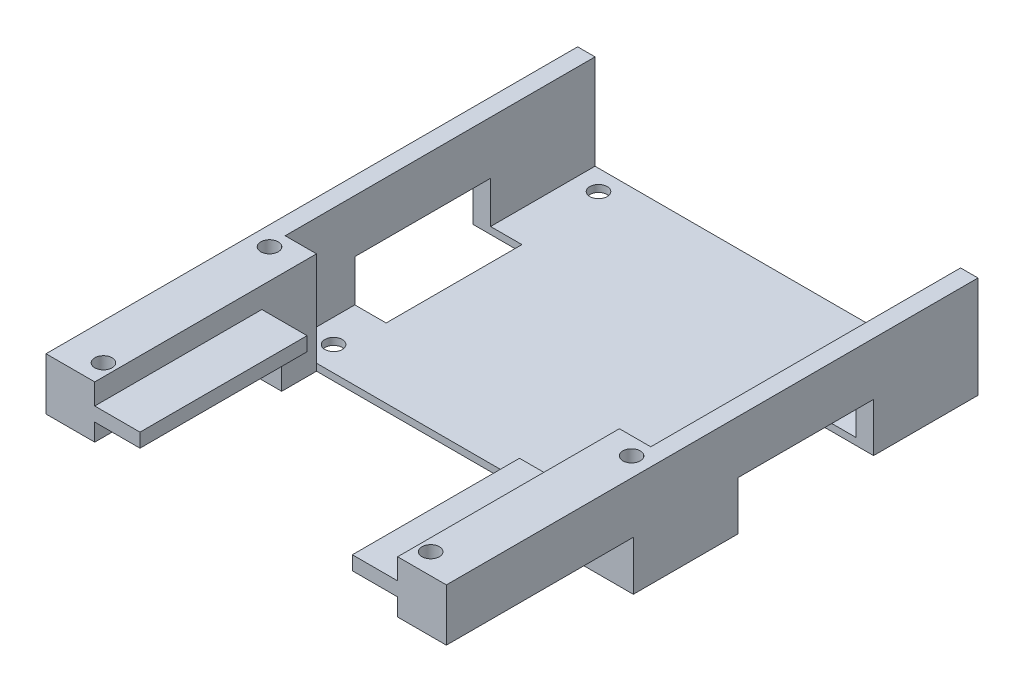
SolidWorks part; units mm, degrees
ref_plane "Front Plane" through (0, 0, 0) normal (0, 0, 1) x (1, 0, 0)
ref_plane "Top Plane" through (0, 0, 0) normal (0, 1, 0) x (1, 0, 0)
ref_plane "Right Plane" through (0, 0, 0) normal (1, 0, 0) x (0, 0, -1)
sketch "Sketch1" plane through (0, 0, 0) normal (0, 1, 0) x (1, 0, 0)
  line L0 (0, 0) -> (0, 76.35) construction
  line L1 (-28.75, 76.35) -> (28.75, 76.35)
  line L2 (28.75, 76.35) -> (28.75, 0)
  line L3 (28.75, 0) -> (21.75, 0)
  line L4 (21.75, 0) -> (21.75, 31.85)
  line L5 (21.75, 31.85) -> (-21.75, 31.85)
  line L6 (-21.75, 31.85) -> (-21.75, 0)
  line L7 (-21.75, 0) -> (-28.75, 0)
  line L8 (-28.75, 0) -> (-28.75, 76.35)
  line L9 (-26.25, 76.35) -> (-26.25, 31.85)
  line L14 (-26.25, 31.85) -> (-21.75, 31.85)
  line L15 (26.25, 76.35) -> (26.25, 31.85)
  line L16 (26.25, 31.85) -> (21.75, 31.85)
  line L17 (28.75, 74.35) -> (30.25, 74.35)
  line L18 (-28.75, 41.35) -> (-26.25, 41.35)
  line L19 (-28.75, 41.35) -> (-28.75, 53.35)
  line L20 (-28.75, 53.35) -> (-26.25, 53.35)
  line L21 (-26.25, 41.35) -> (-26.25, 53.35)
  line L22 (30.25, 68.35) -> (28.75, 68.35)
  line L23 (-30.25, 68.35) -> (-28.75, 68.35)
  line L24 (-28.75, 74.35) -> (-30.25, 74.35)
  arc A0 (30.25, 68.35) -> (30.25, 74.35) centre (30.25, 71.35) ccw
  arc A1 (-30.25, 68.35) -> (-30.25, 74.35) centre (-30.25, 71.35) cw
  point P10 (0, 76.35)
  point P16 (-27.5, 41.35)
  point P17 (-22.85, 73.45)
  point P18 (22.85, 73.45)
  point P23 (22.85, 35.4)
  point P24 (-22.85, 35.4)
  point P25 (23.5, 3)
  point P26 (26, 29.35)
  point P27 (-26, 29.35)
  point P28 (-23.5, 3)
  point P40 (30.25, 71.35)
  point P41 (-30.25, 71.35)
  dimension "D16" = 3
  dimension "D1" = 2.5
  dimension "D2" = 7
  dimension "D3" = 43.5
  dimension "D4" = 31.85
  dimension "D5" = 44.5
  dimension "D6" = 23
  dimension "D7" = 12
  dimension "D8" = 22.85
  dimension "D9" = 38.05
  dimension "D10" = 2.9
  dimension "D11" = 47
  dimension "D12" = 52
  dimension "D13" = 47
  dimension "D14" = 3
  dimension "D15" = 1.5
  dimension "D17" = 2
extrude "Boss-Extrude1" add sketch "Sketch1" along normal blind 1 contours L5 L0 L1 L9 L14 | L0 L5 L16 L15 L1 region at (-13.125, 0, -54.1) region at (13.125, 0, -54.1)
extrude "Boss-Extrude2" add sketch "Sketch1<3>" along normal blind 14.6 contours L18 L8 L7 L6 L14 L9 | L8 L20 L9 L1 | L15 L16 L4 L3 L2 L1 | L20 L8 L18 L9 region at (-27.5, 0, -64.85) region at (25.999, 0, -28.6329) region at (-27.5, 0, -47.35) region at (-25.4666, 0, -17.9154)
sketch "Sketch1<3>" plane through (0, 0, 0) normal (0, 1, 0) x (1, 0, 0) same geometry as "Sketch1"
hole_wizard "Ø2.5 (2.5) Diameter Hole1" positions "Sketch4" profile "Sketch5" hole size "Ø2.5" standard "ANSI Metric" end condition through all
sketch "Sketch4" plane through (0, 0, 0) normal (0, -1, 0) x (-1, 0, 0)
  point P0 (-22.85, 73.45)
  point P3 (22.85, 73.45)
  point P6 (26, 29.35)
  point P9 (22.85, 35.4)
  point P12 (-22.85, 35.4)
  point P15 (-26, 29.35)
  point P18 (-23.5, 3)
  point P21 (23.5, 3)
  point P24 (-30.25, 71.35)
  point P27 (30.25, 71.35)
sketch "Sketch5" plane through (22.85, 0, -73.45) normal (1, 0, 0) x (0, 0, -1)
  line L0 (0, 0) -> (0, 14.6)
  line L1 (0, 14.6) -> (1.25, 14.6)
  line L2 (1.25, 14.6) -> (1.25, 0)
  line L5 (1.25, 0) -> (0, 0)
  line L11 (0, -6.35) -> (0, 107.95) construction
  dimension "Thru Hole Dia." = 2.5
  dimension "Thru Hole Depth" = 14.6
sketch "Sketch6" plane through (0, 0, 0) normal (0, 0, 1) x (1, 0, 0)
  line L0 (-21.75, 14.6) -> (-21.75, 0) construction
  line L5 (0, -1.6497) -> (0, 21.9352) construction
  line L6 (-21.75, 9.6) -> (-15.25, 9.6)
  line L7 (-21.75, 9.6) -> (-21.75, 11.6)
  line L8 (-21.75, 11.6) -> (-15.25, 11.6)
  line L9 (-15.25, 9.6) -> (-15.25, 11.6)
  line L10 (-28.75, 14.6) -> (-28.75, 0) construction
  line L11 (-20.25, 9.6) -> (-21.75, 9.6)
  line L12 (-20.25, 9.6) -> (-20.25, 7.1)
  line L13 (-20.25, 7.1) -> (-21.75, 7.1)
  line L14 (-21.75, 9.6) -> (-21.75, 7.1)
  line L15 (-21.75, 0) -> (-28.75, 0)
  line L16 (-21.75, 0) -> (-21.75, 7.1)
  line L17 (-21.75, 7.1) -> (-28.75, 7.1)
  line L18 (-28.75, 0) -> (-28.75, 7.1)
  line L19 (28.75, 0) -> (28.75, 7.1)
  line L20 (21.75, 7.1) -> (28.75, 7.1)
  line L21 (21.75, 0) -> (21.75, 7.1)
  line L22 (21.75, 0) -> (28.75, 0)
  line L23 (21.75, 9.6) -> (21.75, 7.1)
  line L24 (20.25, 7.1) -> (21.75, 7.1)
  line L25 (20.25, 9.6) -> (20.25, 7.1)
  line L26 (20.25, 9.6) -> (21.75, 9.6)
  line L27 (15.25, 9.6) -> (15.25, 11.6)
  line L28 (21.75, 11.6) -> (15.25, 11.6)
  line L29 (21.75, 9.6) -> (21.75, 11.6)
  line L30 (21.75, 9.6) -> (15.25, 9.6)
  line L31 (-21.75, 14.6) -> (-28.75, 14.6) construction
  line M21 (21.75, 0) -> (28.75, 0)
  line M22 (28.75, 0) -> (28.75, 14.6)
  line M24 (21.75, 14.6) -> (21.75, 0)
  dimension "D1" = 6.5
  dimension "D2" = 3
  dimension "D3" = 2
  dimension "D4" = 2.5
  dimension "D5" = 1.5
extrude "Boss-Extrude3" add sketch "Sketch6" against normal blind 24 contours L30 L26 L28 L27 M24 | L6 L9 L8 L7 region at (-18.5, 10.6, 0) region at (18.5, 10.6, 0)
extrude "Cut-Extrude1" cut sketch "Sketch6<4>" against normal blind 26.85 contours L18 L15 L16 L17 | L20 M24 M21 M22 region at (-25.25, 3.55, 0) region at (25.25, 3.55, 0)
sketch "Sketch6<4>" plane through (0, 0, 0) normal (0, 0, 1) x (1, 0, 0) same geometry as "Sketch6"
sketch "Sketch8" plane through (0, 0, 0) normal (0, -1, 0) x (1, 0, 0)
  line L0 (0, 17.5937) -> (0, -89.2896) construction
  line L1 (-28.75, -61.35) -> (-21.75, -61.35)
  line L2 (-28.75, -61.35) -> (-28.75, -41.85)
  line L3 (-28.75, -41.85) -> (-21.75, -41.85)
  line L4 (-21.75, -61.35) -> (-21.75, -41.85)
  line L6 (-28.75, -76.35) -> (28.75, -76.35) construction
  line L8 (21.75, -61.35) -> (21.75, -41.85)
  line L9 (28.75, -41.85) -> (21.75, -41.85)
  line L10 (28.75, -61.35) -> (28.75, -41.85)
  line L11 (28.75, -61.35) -> (21.75, -61.35)
  line L12 (-28.75, -26.85) -> (-28.75, -76.35) construction
  dimension "D1" = 15
  dimension "D2" = 7
  dimension "D3" = 19.5
extrude "Cut-Extrude2" cut sketch "Sketch8" against normal blind 7
sketch "Sketch9" plane through (0, 0, 0) normal (0, -1, 0) x (1, 0, 0)
  line L0 (-3.6898, -66.9636) -> (-0.7669, -56.1918)
  line L1 (-0.7669, -56.1918) -> (-9.5993, -56.1918)
  line L2 (-9.5993, -56.1918) -> (4.2079, -40.0618)
  line L3 (4.2079, -40.0618) -> (3.001, -51.0446)
  line L4 (3.001, -51.0446) -> (10.9951, -51.0446)
  line L5 (10.9951, -51.0446) -> (-3.6898, -66.9636)
extrude "Cut-Extrude3" cut sketch "Sketch9" against normal blind 0.1
equation "\"D1@Boss-Extrude2\"=16.000000mm-1.4"
